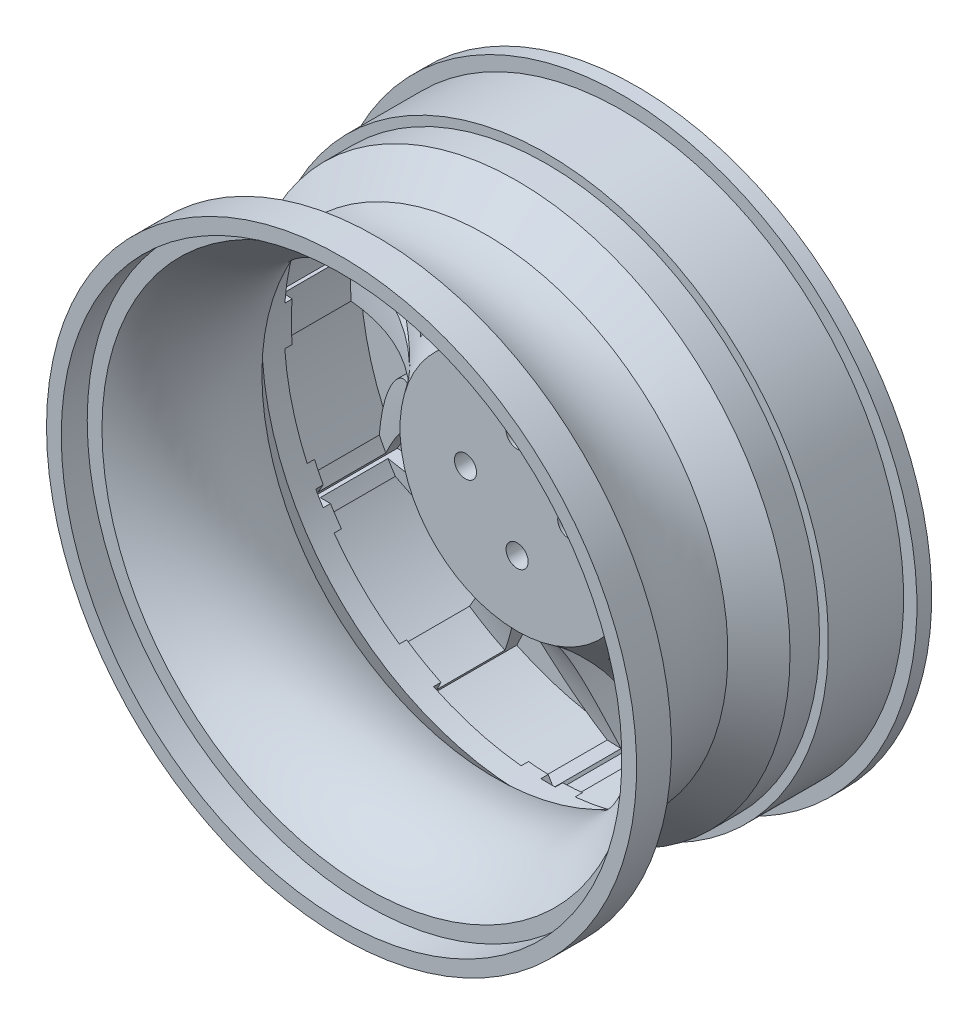
SolidWorks part; units mm, degrees
ref_plane "Ön Düzlem" through (0, 0, 0) normal (0, 0, 1) x (1, 0, 0)
ref_plane "Üst Düzlem" through (0, 0, 0) normal (0, 1, 0) x (1, 0, 0)
ref_plane "Sağ Düzlem" through (0, 0, 0) normal (1, 0, 0) x (0, 0, -1)
sketch "Çizim3" plane through (0, 0, 0) normal (1, 0, 0) x (0, 0, -1)
  line L0 (0, 0) -> (-301.6955, 0) construction
  line L1 (0, 185) -> (0, 200)
  line L2 (0, 200) -> (-10, 200)
  line L3 (-10, 200) -> (-10, 191)
  line L4 (-10, 191) -> (-61, 191)
  line L5 (-61, 191) -> (-61, 185)
  line L6 (-61, 185) -> (-81, 185)
  line L7 (0, 185) -> (-55, 185)
  line L8 (-55, 185) -> (-55, 179)
  line L9 (-55, 179) -> (-75, 179)
  line L10 (-81, 185) -> (-102.0614, 163.9386)
  line L11 (-75, 179) -> (-96.0614, 157.9386)
  line L12 (-176.4, 200) -> (-200, 200)
  line L13 (-200, 200) -> (-200, 190)
  line L14 (-200, 190) -> (-182.4, 190)
  line L15 (-182.4, 190) -> (-182.4, 180)
  line L16 (-176.4, 200) -> (-176.4, 185)
  spline S0 degree 2 poles (-176.4, 185) (-145.5259, 152.8597) (-102.0614, 163.9386) knots 0 0 0 1 1 1
  spline S1 degree 2 poles (-182.4, 180) (-146.3686, 138.9383) (-96.0614, 157.9386) knots 0 0 0 1 1 1
  dimension "D1" = 200
  dimension "D2" = 15
  dimension "D3" = 10
  dimension "D4" = 55
  dimension "D5" = 6
  dimension "D6" = 6
  dimension "D7" = 6
  dimension "D8" = 20
  dimension "D9" = 20
  dimension "D10" = 200
  dimension "D11" = 10
  dimension "D12" = 17.6
  dimension "D13" = 15
  dimension "D14" = 10
  dimension "D15" = 6
revolve "Döndür1" add sketch "Çizim3" angle 360 about L0
sketch "Çizim5" plane through (0, 0, 0) normal (1, 0, 0) x (0, 0, -1)
  line L0 (-81, 79.4) -> (-81, 50)
  line L1 (0, 0) -> (-477.2243, 0) construction
  line L2 (0, 197.3) -> (-7.5, 197.3)
  line L3 (0, -200) -> (0, 200) construction
  line L4 (-81, 185) -> (-81, -185) construction
  line L5 (-81, 50) -> (-46, 50)
  spline S0 degree 2 poles (-81, 79.4) (-14.1232, 122.5201) (-7.5, 197.3) knots 0 0 0 1 1 1
  spline S1 degree 2 poles (-46, 50) (10.0546, 118.5356) (0, 197.3) knots 0 0 0 1 1 1
  dimension "D1" = 2.7
  dimension "D2" = 7.5
  dimension "D3" = 35
  dimension "D4" = 79.4
  dimension "D5" = 50
revolve "Döndür4" add sketch "Çizim5" angle 360 about L1
sketch "Çizim8" plane through (0, 0, 0) normal (0, 0, 1) x (1, 0, 0)
  line L0 (0, 0) -> (0, -226.2891) construction
  line L1 (0, 0) -> (99.928, -207.5423) construction
  line L2 (0, -77.3) -> (0, -187.3)
  line L3 (28.2907, -58.7575) -> (81.2538, -168.7575)
  circle A0 centre (0, 0) radius 187.3
  spline S0 degree 2 poles (0, -187.3) (35.6262, -131.2321) (0, -77.3) knots 0 0 0 1 1 1
  spline S1 degree 2 poles (28.2907, -58.7575) (71.396, -137.3551) (7.8258, -187.1364) knots 0 0 0 1 1 1
  dimension "D1" = 374.6
  dimension "D2" = 25.71
  dimension "D3" = 110
  dimension "D4" = 110
extrude "Kes-Ekstrüzyon7" cut sketch "Çizim8" along normal blind 60 contours L2 S0 | L3 S1 A0 region at (7.1252, -132.0864, 0) region at (50.1605, -154.1365, 0)
mirror "Aynalama5" about plane through (0, 0, 0) normal (1, 0, 0) of "Kes-Ekstrüzyon7"
pattern_circular "Dairesel Kaplama6" count 6 over 360 about axis through (0, 0, 0) along (0, 0, -1) of "Aynalama5"
sketch "Çizim9" plane through (0, 0, 0) normal (1, 0, 0) x (0, 0, -1)
  line L0 (-51, 0) -> (-81, 0)
  line L1 (-81, 185) -> (-81, -185) construction
  line L2 (-81, 0) -> (-81, 50)
  line L3 (-81, 50) -> (-38.151, 50)
  spline S0 degree 2 poles (-51, 0) (-40.8146, 24.0714) (-38.151, 50) knots 0 0 0 1 1 1
  dimension "D1" = 30
  dimension "D2" = 50
revolve "Döndür5" add sketch "Çizim9" angle 360 about L0
sketch "Çizim10" plane through (0, 0, 81) normal (0, 0, 1) x (1, 0, 0)
  circle A0 centre (0, 0) radius 35
  circle A1 centre (0, 35) radius 7.5
  dimension "D1" = 70
  dimension "D2" = 15
extrude "Kes-Ekstrüzyon14" cut sketch "Çizim10" against normal blind 4855 contours A0 A1 | A0 A1 region at (0, 31.6766, 81) region at (0, 38.034, 81)
pattern_circular "Dairesel Kaplama8" count 4 over 360 about axis through (0, 0, 0) along (0, 0, 1) of "Kes-Ekstrüzyon14"
